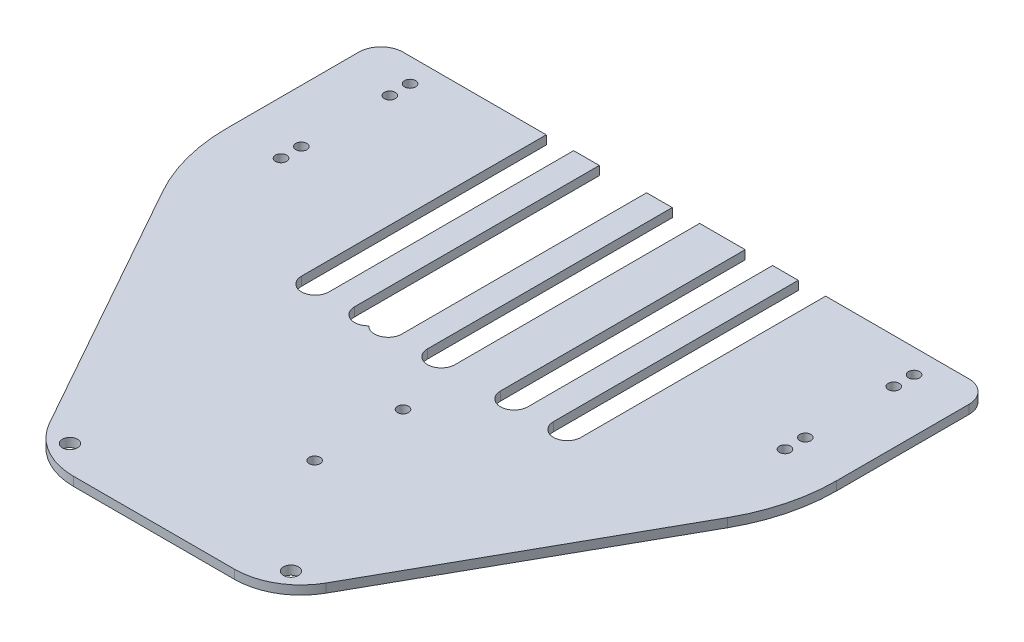
SolidWorks part; units mm, degrees
material "6061 Alloy"
ref_plane "Front Plane" through (0, 0, 0) normal (0, 0, 1) x (1, 0, 0)
ref_plane "Top Plane" through (0, 0, 0) normal (0, 1, 0) x (1, 0, 0)
ref_plane "Right Plane" through (0, 0, 0) normal (1, 0, 0) x (0, 0, -1)
sketch "Sketch1" plane through (0, 0, 0) normal (0, 1, 0) x (1, 0, 0)
  line L1 (0, 0) -> (138, 0)
  line L2 (0, 0) -> (0, 120.35)
  line L3 (0, 120.35) -> (138, 120.35)
  line L4 (138, 0) -> (138, 120.35)
  dimension "D1" = 138
  dimension "D2" = 120.35
extrude "Boss-Extrude1" add sketch "Sketch1" along normal blind 2
sketch "Sketch3" plane through (0, 2, 0) normal (0, 1, 0) x (1, 0, 0)
  line L0 (88.6, 120.35) -> (88.6, 65)
  line L2 (88.6, 120.35) -> (82.4, 120.35)
  line L3 (82.4, 120.35) -> (82.4, 65)
  line L4 (72.1, 120.35) -> (72.1, 65)
  line L5 (72.1, 120.35) -> (65.9, 120.35)
  line L6 (65.9, 120.35) -> (65.9, 65)
  line L7 (100.6, 120.35) -> (100.6, 65)
  line L8 (100.6, 120.35) -> (94.4, 120.35)
  line L9 (94.4, 120.35) -> (94.4, 65)
  line L10 (60.1, 120.35) -> (60.1, 65)
  line L11 (60.1, 120.35) -> (53.9, 120.35)
  line L12 (53.9, 120.35) -> (53.9, 65)
  line L16 (43.6, 120.35) -> (43.6, 65)
  line L17 (43.6, 120.35) -> (37.4, 120.35)
  line L18 (37.4, 120.35) -> (37.4, 65)
  line L19 (138, 120.35) -> (0, 120.35) construction
  line L23 (138, 0) -> (138, 120.35) construction
  arc A0 (82.4, 65) -> (88.6, 65) centre (85.5, 65) ccw
  arc A1 (65.9, 65) -> (72.1, 65) centre (69, 65) ccw
  arc A2 (94.4, 65) -> (100.6, 65) centre (97.5, 65) ccw
  arc A3 (53.9, 65) -> (60.1, 65) centre (57, 65) ccw
  arc A5 (37.4, 65) -> (43.6, 65) centre (40.5, 65) ccw
  dimension "D1" = 3.1
  dimension "D2" = 16.5
  dimension "D4" = 12
  dimension "D5" = 16.5
  dimension "D6" = 12
  dimension "D7" = 55.35
  dimension "D8" = 40.5
extrude "Cut-Extrude1" cut sketch "Sketch3" against normal through all
sketch "Sketch4" plane through (0, 2, 0) normal (0, 1, 0) x (1, 0, 0)
  line L0 (49.4, 120.35) -> (55.6, 120.35)
  line L1 (53.9, 120.35) -> (43.6, 120.35) construction
  line L2 (55.6, 120.35) -> (55.6, 65)
  line L3 (49.4, 120.35) -> (49.4, 65)
  line L4 (43.6, 65) -> (43.6, 120.35) construction
  arc A0 (49.4, 65) -> (55.6, 65) centre (52.5, 65) ccw
  arc A1 (53.9, 65) -> (60.1, 65) centre (57, 65) ccw construction
  dimension "D1" = 4.5
extrude "Cut-Extrude2" cut sketch "Sketch4" against normal through all
hole_wizard "linear bearing" positions "Sketch6" profile "Sketch5" tap size "M3x0.5" standard "ANSI Metric" end condition through all
sketch "Sketch6" plane through (0, 2, 0) normal (0, 1, 0) x (1, 0, 0)
  line L0 (138, 0) -> (138, 120.35) construction
  line L6 (0, 120.35) -> (0, 0) construction
  line L9 (37.4, 120.35) -> (0, 120.35) construction
  point P36 (12, 110.35)
  point P38 (12, 90.35)
  point P40 (126, 110.35)
  point P42 (126, 90.35)
  point P44 (75, 50.35)
  point P46 (75, 30.35)
  dimension "D1" = 63
  dimension "D2" = 12
  dimension "D3" = 10
  dimension "D4" = 12
  dimension "D5" = 20
  dimension "D6" = 40
  dimension "D7" = 20
sketch "Sketch5" plane through (12, 2, -110.35) normal (1, 0, 0) x (0, 0, 1)
  line L0 (0, 0) -> (0, 2)
  line L1 (0, 2) -> (1.25, 2)
  line L2 (1.25, 2) -> (1.25, 0)
  line L5 (1.25, 0) -> (0, 0)
  line L11 (0, -6.35) -> (0, 107.95) construction
  dimension "Thread Major Dia." = 2.5
  dimension "Thru Tap Drill Depth" = 2
hole_wizard "belt holders" positions "Sketch8" profile "Sketch7" tap size "M3x0.5" standard "ANSI Metric" end condition through all
sketch "Sketch8" plane through (0, 2, 0) normal (0, 1, 0) x (1, 0, 0)
  line L0 (0, 120.35) -> (0, 0) construction
  line L1 (138, 0) -> (138, 120.35) construction
  circle A0 centre (12, 110.35) radius 1.25 construction
  circle A1 centre (12, 90.35) radius 1.25 construction
  point P0 (12, 114.95)
  point P2 (12, 85.75)
  point P4 (126, 85.75)
  point P6 (126, 114.95)
  dimension "D2" = 4.6
  dimension "D1" = 12
  dimension "D3" = 4.6
  dimension "D4" = 12
cosmetic thread "Hole Thread1" parameters "D2"=3
cosmetic thread "Hole Thread2" parameters "D2"=3
cosmetic thread "Hole Thread3" parameters "D2"=3
cosmetic thread "Hole Thread4" parameters "D2"=3
sketch "Sketch7" plane through (12, 2, -114.95) normal (1, 0, 0) x (0, 0, 1)
  line L0 (0, 0) -> (0, 2)
  line L1 (0, 2) -> (1.25, 2)
  line L2 (1.25, 2) -> (1.25, 0)
  line L5 (1.25, 0) -> (0, 0)
  line L11 (0, -6.35) -> (0, 107.95) construction
  dimension "Thru Tap Drill Dia." = 2.5
  dimension "Thru Tap Drill Depth" = 2
hole_wizard "Ø3.4 (3.4) Diameter Hole1" positions "Sketch11" profile "Sketch10" hole size "Ø3.4" standard "ANSI Metric" end condition through all
sketch "Sketch11" plane through (0, 2, 0) normal (0, 1, 0) x (1, 0, 0)
  line L2 (0, 0) -> (138, 0) construction
  line L3 (138, 0) -> (138, 120.35) construction
  point P2 (94, 6)
  point P4 (44, 6)
  dimension "D1" = 6
  dimension "D2" = 50
  dimension "D3" = 44
sketch "Sketch10" plane through (94, 2, -6) normal (1, 0, 0) x (0, 0, 1)
  line L0 (0, 0) -> (0, 2)
  line L1 (0, 2) -> (1.7, 2)
  line L2 (1.7, 2) -> (1.7, 0)
  line L5 (1.7, 0) -> (0, 0)
  line L11 (0, -6.35) -> (0, 107.95) construction
  dimension "Thru Hole Dia." = 3.4
  dimension "Thru Hole Depth" = 2
sketch "Sketch9" plane through (0, 2, 0) normal (0, 1, 0) x (1, 0, 0)
  line L0 (0, 75) -> (42, 0)
  line L1 (0, 120.35) -> (0, 0) construction
  line L2 (0, 0) -> (138, 0) construction
  line L3 (42, 0) -> (0, 0)
  line L4 (0, 0) -> (0, 75)
  line L5 (138, 0) -> (138, 75)
  line L6 (138, 0) -> (138, 120.35) construction
  line L7 (138, 75) -> (96, 0)
  line L8 (96, 0) -> (138, 0)
  dimension "D1" = 42
  dimension "D2" = 75
extrude "Cut-Extrude3" cut sketch "Sketch9" against normal through all
fillet "Fillet1" radius 5 2 edges at (138, 1, -120.35) (0, 1, -120.35)
fillet "Fillet2" radius 40 2 edges at (138, 1, -75) (0, 1, -75)
fillet "Fillet3" radius 15 2 edges at (96, 1, 0) (42, 1, 0)
